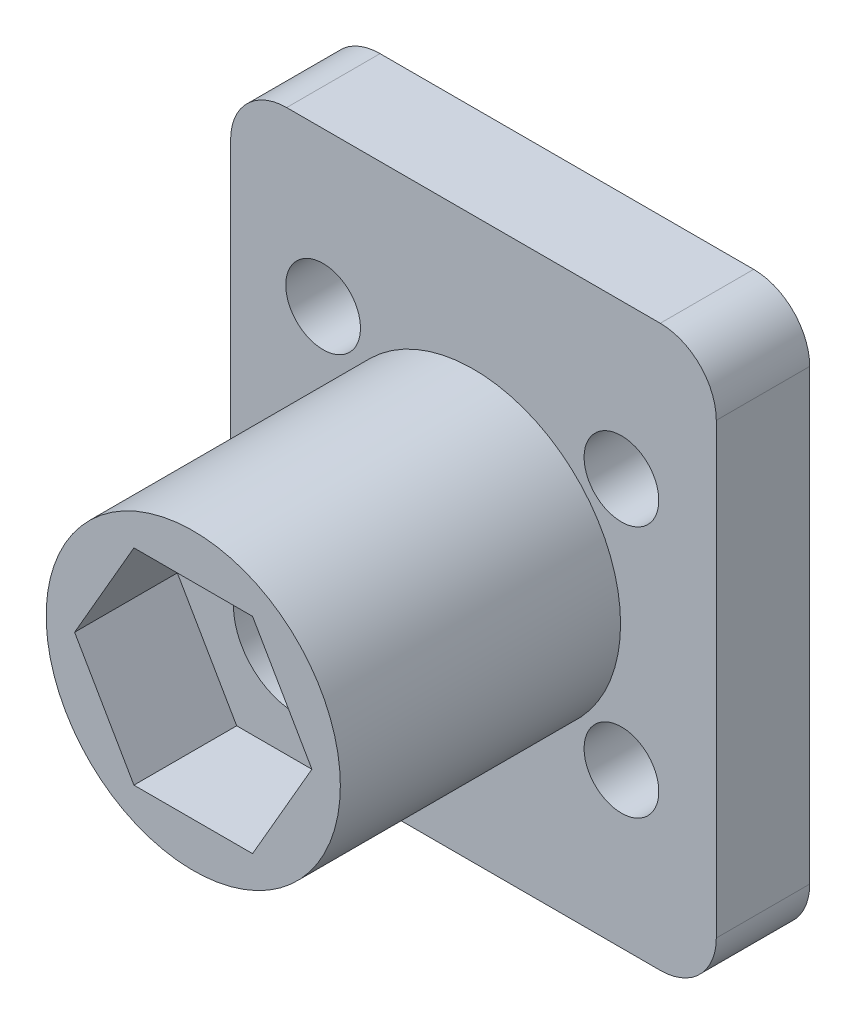
SolidWorks part; units mm, degrees
material "PLA"
ref_plane "Plan de face" through (0, 0, 0) normal (0, 0, 1) x (1, 0, 0)
ref_plane "Plan de dessus" through (0, 0, 0) normal (0, 1, 0) x (1, 0, 0)
ref_plane "Plan de droite" through (0, 0, 0) normal (1, 0, 0) x (0, 0, -1)
sketch "Esquisse1" plane through (0, 0, 0) normal (0, 0, 1) x (1, 0, 0)
  line L1 (6.3509, 0) -> (3.1754, 5.5)
  line L2 (3.1754, 5.5) -> (-3.1754, 5.5)
  line L3 (-3.1754, 5.5) -> (-6.3509, 0)
  line L4 (-6.3509, 0) -> (-3.1754, -5.5)
  line L5 (-3.1754, -5.5) -> (3.1754, -5.5)
  line L6 (3.1754, -5.5) -> (6.3509, 0)
  circle A0 centre (0, 0) radius 5.5 construction
  circle A1 centre (0, 0) radius 7.875
  dimension "D2" = 15.75
  dimension "D1" = 11
extrude "Boss.-Extru.1" add sketch "Esquisse1" along normal blind 15
sketch "Esquisse2" plane through (0, 0, 0) normal (0, 0, -1) x (-1, 0, 0)
  line L1 (-13, 15) -> (13, 15)
  line L2 (-13, 15) -> (-13, -15)
  line L3 (-13, -15) -> (13, -15)
  line L4 (13, 15) -> (13, -15)
  line L5 (-13, 15) -> (13, -15) construction
  line L6 (-13, -15) -> (13, 15) construction
  point P0 (0, 0)
  dimension "D1" = 26
  dimension "D2" = 13
  dimension "D3" = 15
  dimension "D4" = 15
extrude "Boss.-Extru.2" add sketch "Esquisse2" along normal blind 5
sketch "Esquisse3" plane through (0, 0, 0) normal (0, 0, 1) x (1, 0, 0)
  line L6 (-3.1754, -5.5) -> (3.1754, -5.5)
  line L7 (3.1754, -5.5) -> (6.3509, 0)
  line L8 (6.3509, 0) -> (3.1754, 5.5)
  line L9 (3.1754, 5.5) -> (-3.1754, 5.5)
  line L10 (-3.1754, 5.5) -> (-6.3509, 0)
  line L11 (-6.3509, 0) -> (-3.1754, -5.5)
  line L12 (-3.1754, -5.5) -> (3.1754, -5.5)
  line L13 (3.1754, -5.5) -> (6.3509, 0)
  line L14 (6.3509, 0) -> (3.1754, 5.5)
  line L15 (3.1754, 5.5) -> (-3.1754, 5.5)
  line L16 (-3.1754, 5.5) -> (-6.3509, 0)
  line L17 (-6.3509, 0) -> (-3.1754, -5.5)
  circle A0 centre (0, 0) radius 3.35
  dimension "D2" = 6.7
  dimension "D1" = 0
extrude "Boss.-Extru.3" add sketch "Esquisse3" along normal blind 9.5
sketch "Esquisse4" plane through (0, 0, 9.5) normal (0, 0, 1) x (1, 0, 0)
  circle A0 centre (0, 0) radius 3.35 construction
  circle A1 centre (0, 0) radius 3.35
extrude "Enlèv. mat.-Extru.1" cut sketch "Esquisse4" against normal blind 19.5
sketch "Esquisse5" plane through (0, 0, -5) normal (0, 0, -1) x (-1, 0, 0)
  line L0 (-7.9217, 6.75) -> (8.0475, 6.75) construction
  line L2 (-7.9217, -6.75) -> (8.0475, -6.75) construction
  circle A0 centre (-7.9217, 6.75) radius 2
  circle A1 centre (8.0475, 6.75) radius 2
  circle A2 centre (-7.9217, -6.75) radius 2
  circle A3 centre (8.0475, -6.75) radius 2
  point P8 (0, 0)
  dimension "D1" = 6.75
  dimension "D2" = 4
  dimension "D3" = 13.5
extrude "Enlèv. mat.-Extru.2" cut sketch "Esquisse5" against normal blind 9.5
fillet "Congé1" radius 3 4 edges at (13, 15, -2.5) (-13, -15, -2.5) (-13, 15, -2.5) (13, -15, -2.5)
